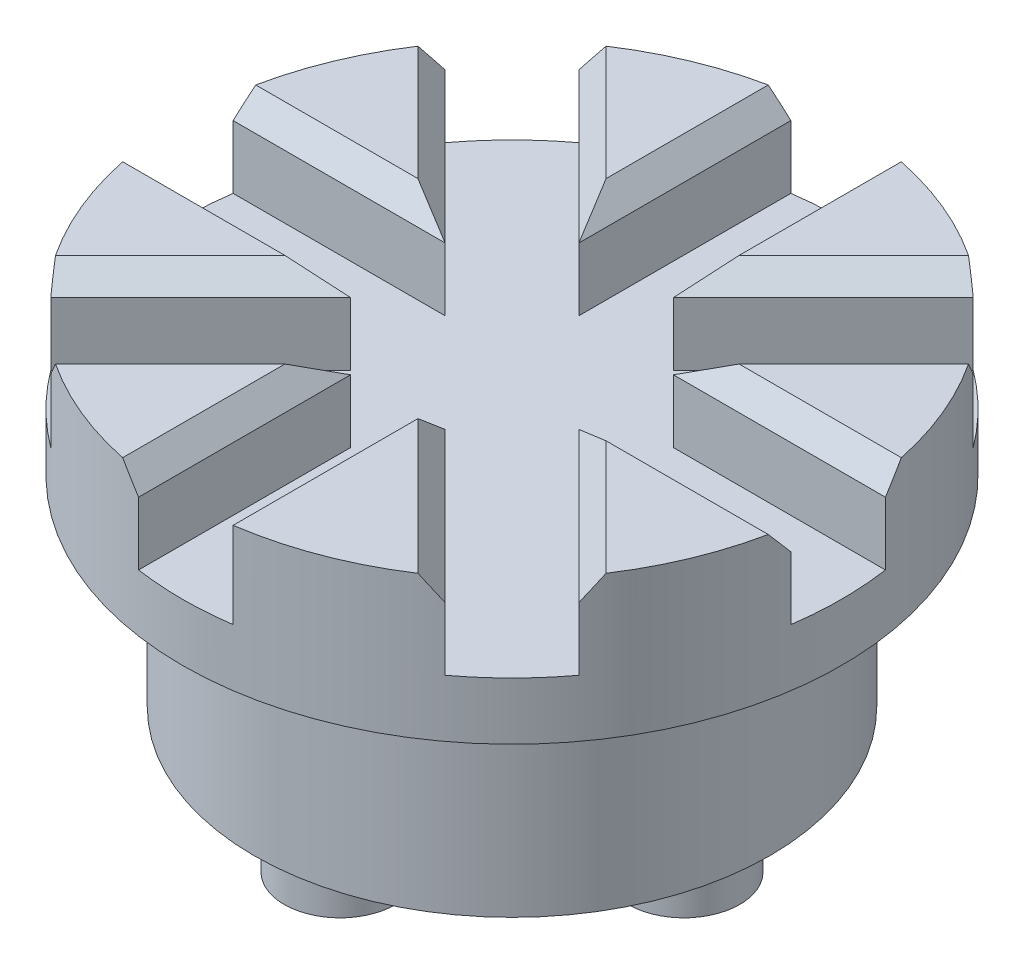
SolidWorks part; units mm, degrees
ref_plane "Front Plane" through (0, 0, 0) normal (0, 0, 1) x (1, 0, 0)
ref_plane "Top Plane" through (0, 0, 0) normal (0, 1, 0) x (1, 0, 0)
ref_plane "Right Plane" through (0, 0, 0) normal (1, 0, 0) x (0, 0, -1)
ref_axis "Axis1" through (0, 12.7, 0) along (0, -1, 0)
sketch "Sketch1" plane through (0, 0, 0) normal (0, 1, 0) x (1, 0, 0)
  line L0 (0, 9) -> (0, -9) construction
  line L1 (-6.364, 6.364) -> (6.364, -6.364) construction
  line L2 (-9, 0) -> (9, 0) construction
  line L3 (-6.364, -6.364) -> (6.364, 6.364) construction
  circle A0 centre (0, 0) radius 9
  circle A1 centre (0, 0) radius 6 construction
  circle A2 centre (-6, 0) radius 1.95
  circle A5 centre (0, 6) radius 1.95
  circle A6 centre (6, 0) radius 1.95
  circle A7 centre (0, -6) radius 1.95
  point P11 (0, 0)
  point P15 (0, 0)
  point P26 (0, 0)
  point P29 (0, 0)
  dimension "D1" = 18
  dimension "D2" = 12
  dimension "D5" = 3.9
  dimension "D6" = 4
  dimension "D3" = 45
  dimension "D4" = 45
extrude "Boss-Extrude1" add sketch "Sketch1" along normal blind 12 contours A0 A7 A6 A5 A2 | A6 | A5 | A2 | A7 region at (0, 0, 0) region at (-6, 0, 0) region at (0, 0, -6) region at (6, 0, 0) region at (0, 0, 6)
extrude "Boss-Extrude2" add sketch "Sketch1<3>" along direction (0, 1, 0) on the side against the normal blind 2 contours A2 | A7 | A6 | A5 region at (-6, 0, 0)
sketch "Sketch1<3>" plane through (0, 0, 0) normal (0, 1, 0) x (1, 0, 0) same geometry as "Sketch1"
sketch "Sketch4" plane through (0, 12, 0) normal (0, 1, 0) x (1, 0, 0)
  circle A0 centre (0, 0) radius 11.5
  circle A1 centre (0, 0) radius 9
  dimension "D1" = 23
  dimension "D2" = 18
extrude "Boss-Extrude3" add sketch "Sketch4" against normal blind 5
sketch "Sketch3" plane through (0, 12, 0) normal (0, 1, 0) x (1, 0, 0)
  line L1 (1.65, 12.1888) -> (1.65, 3.9835)
  line L6 (9.7855, 7.4521) -> (3.9835, 1.65)
  line L9 (12.1888, -1.65) -> (3.9835, -1.65)
  line L12 (7.4521, -9.7855) -> (1.65, -3.9835)
  line L15 (-1.65, -12.1888) -> (-1.65, -3.9835)
  line L18 (-9.7855, -7.4521) -> (-3.9835, -1.65)
  line L21 (-12.1888, 1.65) -> (-3.9835, 1.65)
  line L24 (-7.4521, 9.7855) -> (-1.65, 3.9835)
  line L26 (-1.65, 3.9835) -> (-1.65, 12.1888)
  line L28 (1.65, 3.9835) -> (7.4521, 9.7855)
  line L30 (3.9835, 1.65) -> (12.1888, 1.65)
  line L32 (3.9835, -1.65) -> (9.7855, -7.4521)
  line L34 (1.65, -3.9835) -> (1.65, -12.1888)
  line L36 (-1.65, -3.9835) -> (-7.4521, -9.7855)
  line L38 (-3.9835, -1.65) -> (-12.1888, -1.65)
  line L40 (-3.9835, 1.65) -> (-9.7855, 7.4521)
  arc A12 (1.65, 12.1888) -> (-1.65, 12.1888) centre (0, 0) ccw
  arc A13 (9.7855, 7.4521) -> (7.4521, 9.7855) centre (0, 0) ccw
  arc A14 (12.1888, -1.65) -> (12.1888, 1.65) centre (0, 0) ccw
  arc A15 (7.4521, -9.7855) -> (9.7855, -7.4521) centre (0, 0) ccw
  arc A16 (-1.65, -12.1888) -> (1.65, -12.1888) centre (0, 0) ccw
  arc A17 (-9.7855, -7.4521) -> (-7.4521, -9.7855) centre (0, 0) ccw
  arc A18 (-12.1888, 1.65) -> (-12.1888, -1.65) centre (0, 0) ccw
  arc A19 (-7.4521, 9.7855) -> (-9.7855, 7.4521) centre (0, 0) ccw
  circle M17 centre (0, 0) radius 12.3
  dimension "D1" = 3.3
  dimension "D3" = 12.3
  dimension "D4" = 1.65
  dimension "D2" = 8
extrude "Cut-Extrude2" cut sketch "Sketch3" against normal blind 3 contours L40 L21 L38 L18 L36 L15 L34 L12 L32 L9 L30 L6 L28 L1 L26 L24 M17 region at (0, 12, 0)
chamfer "Chamfer1" distance 0.8 angle 40 15 edges at (-7.6822, 12, 1.65) (-6.5989, 12, 4.2654) (-4.2654, 12, 6.5989) (-1.65, 12, 7.6822) (4.2654, 12, 6.5989) (6.5989, 12, 4.2654) (7.6822, 12, 1.65) (7.6822, 12, -1.65) (6.5989, 12, -4.2654) (4.2654, 12, -6.5989) (1.65, 12, -7.6822) (-1.65, 12, -7.6822) (-4.2654, 12, -6.5989) (-7.6822, 12, -1.65) (-6.5989, 12, -4.2654) first distance on face at (-7.6822, 10.5, 1.65) first distance on face at (-6.5989, 10.5, 4.2654) first distance on face at (-4.2654, 10.5, 6.5989) first distance on face at (-1.65, 10.5, 7.6822) first distance on face at (4.2654, 10.5, 6.5989) first distance on face at (6.5989, 10.5, 4.2654) first distance on face at (7.6822, 10.5, 1.65) first distance on face at (7.6822, 10.5, -1.65) first distance on face at (6.5989, 10.5, -4.2654) first distance on face at (4.2654, 10.5, -6.5989) first distance on face at (1.65, 10.5, -7.6822) first distance on face at (-1.65, 10.5, -7.6822) first distance on face at (-4.2654, 10.5, -6.5989) first distance on face at (-7.6822, 10.5, -1.65) first distance on face at (-6.5989, 10.5, -4.2654)
